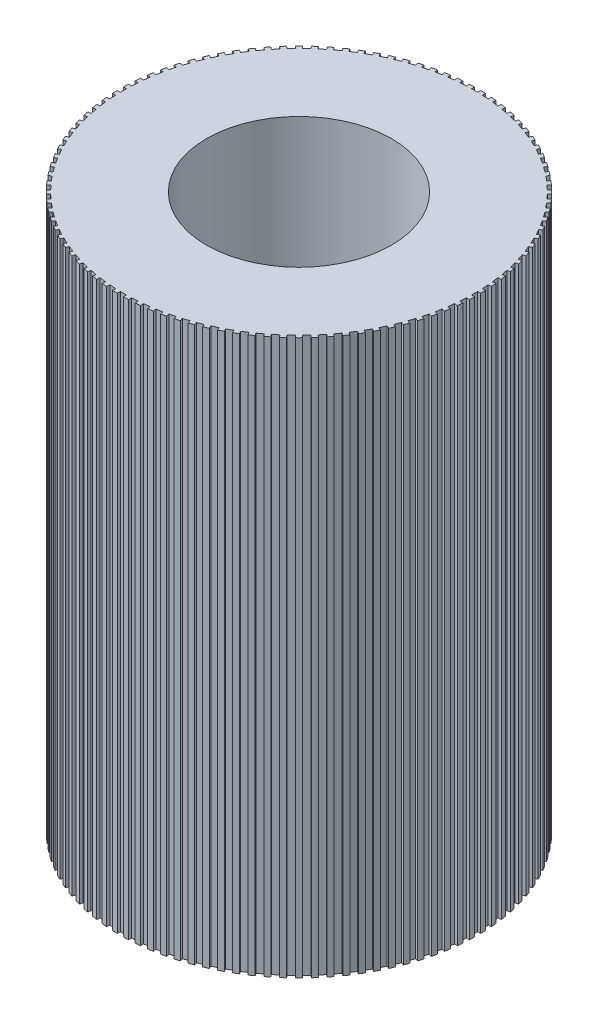
SolidWorks part; units mm, degrees
material "易切削黄铜, UNS C36000"
ref_plane "前视基准面" through (0, 0, 0) normal (0, 0, 1) x (1, 0, 0)
ref_plane "上视基准面" through (0, 0, 0) normal (0, 1, 0) x (1, 0, 0)
ref_plane "右视基准面" through (0, 0, 0) normal (1, 0, 0) x (0, 0, -1)
sketch "草图1" plane through (0, 0, 0) normal (0, 1, 0) x (1, 0, 0)
  circle A0 centre (0, 0) radius 2.9
  circle A1 centre (0, 0) radius 1.5
  dimension "D1" = 5.8
  dimension "D2" = 3
extrude "凸台-拉伸1" add sketch "草图1" along normal blind 9
sketch "草图2" plane through (0, 9, 0) normal (0, 1, 0) x (1, 0, 0)
  line L0 (0.1353, 2.9473) -> (0.2351, 2.941)
  line L1 (-0.05, 2.95) -> (0.05, 2.95)
  line L2 (-0.05, 2.95) -> (-0.05, 2.85)
  line L3 (-0.05, 2.85) -> (0.05, 2.85)
  line L4 (0.05, 2.95) -> (0.05, 2.85)
  line L5 (-0.05, 2.95) -> (0.05, 2.85) construction
  line L6 (-0.05, 2.85) -> (0.05, 2.95) construction
  line L7 (0.1353, 2.9473) -> (0.1291, 2.8475)
  line L8 (0.2351, 2.941) -> (0.2289, 2.8412)
  line L9 (0.1291, 2.8475) -> (0.2289, 2.8412)
  line L10 (0.3201, 2.933) -> (0.4193, 2.9205)
  line L11 (0.3201, 2.933) -> (0.3076, 2.8338)
  line L12 (0.4193, 2.9205) -> (0.4068, 2.8213)
  line L13 (0.3076, 2.8338) -> (0.4068, 2.8213)
  line L14 (0.5037, 2.9071) -> (0.6019, 2.8884)
  line L15 (0.5037, 2.9071) -> (0.4849, 2.8089)
  line L16 (0.6019, 2.8884) -> (0.5832, 2.7901)
  line L17 (0.4849, 2.8089) -> (0.5832, 2.7901)
  line L18 (0.6852, 2.8698) -> (0.7821, 2.8449)
  line L19 (0.6852, 2.8698) -> (0.6603, 2.7729)
  line L20 (0.7821, 2.8449) -> (0.7572, 2.748)
  line L21 (0.6603, 2.7729) -> (0.7572, 2.748)
  line L22 (0.864, 2.8211) -> (0.9592, 2.7902)
  line L23 (0.864, 2.8211) -> (0.8331, 2.726)
  line L24 (0.9592, 2.7902) -> (0.9283, 2.6951)
  line L25 (0.8331, 2.726) -> (0.9283, 2.6951)
  line L26 (1.0395, 2.7612) -> (1.1325, 2.7244)
  line L27 (1.0395, 2.7612) -> (1.0027, 2.6683)
  line L28 (1.1325, 2.7244) -> (1.0956, 2.6315)
  line L29 (1.0027, 2.6683) -> (1.0956, 2.6315)
  line L30 (1.2108, 2.6905) -> (1.3013, 2.648)
  line L31 (1.2108, 2.6905) -> (1.1682, 2.6)
  line L32 (1.3013, 2.648) -> (1.2587, 2.5575)
  line L33 (1.1682, 2.6) -> (1.2587, 2.5575)
  line L34 (1.3774, 2.6092) -> (1.465, 2.561)
  line L35 (1.3774, 2.6092) -> (1.3292, 2.5216)
  line L36 (1.465, 2.561) -> (1.4168, 2.4734)
  line L37 (1.3292, 2.5216) -> (1.4168, 2.4734)
  line L38 (1.5385, 2.5176) -> (1.6229, 2.464)
  line L39 (1.5385, 2.5176) -> (1.4849, 2.4331)
  line L40 (1.6229, 2.464) -> (1.5693, 2.3795)
  line L41 (1.4849, 2.4331) -> (1.5693, 2.3795)
  line L42 (1.6935, 2.416) -> (1.7744, 2.3572)
  line L43 (1.6935, 2.416) -> (1.6347, 2.3351)
  line L44 (1.7744, 2.3572) -> (1.7156, 2.2763)
  line L45 (1.6347, 2.3351) -> (1.7156, 2.2763)
  line L46 (1.8419, 2.3049) -> (1.9189, 2.2411)
  line L47 (1.8419, 2.3049) -> (1.7781, 2.2278)
  line L48 (1.9189, 2.2411) -> (1.8552, 2.1641)
  line L49 (1.7781, 2.2278) -> (1.8552, 2.1641)
  line L50 (1.983, 2.1847) -> (2.0559, 2.1162)
  line L51 (1.983, 2.1847) -> (1.9145, 2.1118)
  line L52 (2.0559, 2.1162) -> (1.9874, 2.0433)
  line L53 (1.9145, 2.1118) -> (1.9874, 2.0433)
  line L54 (2.1162, 2.0559) -> (2.1847, 1.983)
  line L55 (2.1162, 2.0559) -> (2.0433, 1.9874)
  line L56 (2.1847, 1.983) -> (2.1118, 1.9145)
  line L57 (2.0433, 1.9874) -> (2.1118, 1.9145)
  line L58 (2.2411, 1.9189) -> (2.3049, 1.8419)
  line L59 (2.2411, 1.9189) -> (2.1641, 1.8552)
  line L60 (2.3049, 1.8419) -> (2.2278, 1.7781)
  line L61 (2.1641, 1.8552) -> (2.2278, 1.7781)
  line L62 (2.3572, 1.7744) -> (2.416, 1.6935)
  line L63 (2.3572, 1.7744) -> (2.2763, 1.7156)
  line L64 (2.416, 1.6935) -> (2.3351, 1.6347)
  line L65 (2.2763, 1.7156) -> (2.3351, 1.6347)
  line L66 (2.464, 1.6229) -> (2.5176, 1.5385)
  line L67 (2.464, 1.6229) -> (2.3795, 1.5693)
  line L68 (2.5176, 1.5385) -> (2.4331, 1.4849)
  line L69 (2.3795, 1.5693) -> (2.4331, 1.4849)
  line L70 (2.561, 1.465) -> (2.6092, 1.3774)
  line L71 (2.561, 1.465) -> (2.4734, 1.4168)
  line L72 (2.6092, 1.3774) -> (2.5216, 1.3292)
  line L73 (2.4734, 1.4168) -> (2.5216, 1.3292)
  line L74 (2.648, 1.3013) -> (2.6905, 1.2108)
  line L75 (2.648, 1.3013) -> (2.5575, 1.2587)
  line L76 (2.6905, 1.2108) -> (2.6, 1.1682)
  line L77 (2.5575, 1.2587) -> (2.6, 1.1682)
  line L78 (2.7244, 1.1325) -> (2.7612, 1.0395)
  line L79 (2.7244, 1.1325) -> (2.6315, 1.0956)
  line L80 (2.7612, 1.0395) -> (2.6683, 1.0027)
  line L81 (2.6315, 1.0956) -> (2.6683, 1.0027)
  line L82 (2.7902, 0.9592) -> (2.8211, 0.864)
  line L83 (2.7902, 0.9592) -> (2.6951, 0.9283)
  line L84 (2.8211, 0.864) -> (2.726, 0.8331)
  line L85 (2.6951, 0.9283) -> (2.726, 0.8331)
  line L86 (2.8449, 0.7821) -> (2.8698, 0.6852)
  line L87 (2.8449, 0.7821) -> (2.748, 0.7572)
  line L88 (2.8698, 0.6852) -> (2.7729, 0.6603)
  line L89 (2.748, 0.7572) -> (2.7729, 0.6603)
  line L90 (2.8884, 0.6019) -> (2.9071, 0.5037)
  line L91 (2.8884, 0.6019) -> (2.7901, 0.5832)
  line L92 (2.9071, 0.5037) -> (2.8089, 0.4849)
  line L93 (2.7901, 0.5832) -> (2.8089, 0.4849)
  line L94 (2.9205, 0.4193) -> (2.933, 0.3201)
  line L95 (2.9205, 0.4193) -> (2.8213, 0.4068)
  line L96 (2.933, 0.3201) -> (2.8338, 0.3076)
  line L97 (2.8213, 0.4068) -> (2.8338, 0.3076)
  line L98 (2.941, 0.2351) -> (2.9473, 0.1353)
  line L99 (2.941, 0.2351) -> (2.8412, 0.2289)
  line L100 (2.9473, 0.1353) -> (2.8475, 0.1291)
  line L101 (2.8412, 0.2289) -> (2.8475, 0.1291)
  line L102 (2.95, 0.05) -> (2.95, -0.05)
  line L103 (2.95, 0.05) -> (2.85, 0.05)
  line L104 (2.95, -0.05) -> (2.85, -0.05)
  line L105 (2.85, 0.05) -> (2.85, -0.05)
  line L106 (2.9473, -0.1353) -> (2.941, -0.2351)
  line L107 (2.9473, -0.1353) -> (2.8475, -0.1291)
  line L108 (2.941, -0.2351) -> (2.8412, -0.2289)
  line L109 (2.8475, -0.1291) -> (2.8412, -0.2289)
  line L110 (2.933, -0.3201) -> (2.9205, -0.4193)
  line L111 (2.933, -0.3201) -> (2.8338, -0.3076)
  line L112 (2.9205, -0.4193) -> (2.8213, -0.4068)
  line L113 (2.8338, -0.3076) -> (2.8213, -0.4068)
  line L114 (2.9071, -0.5037) -> (2.8884, -0.6019)
  line L115 (2.9071, -0.5037) -> (2.8089, -0.4849)
  line L116 (2.8884, -0.6019) -> (2.7901, -0.5832)
  line L117 (2.8089, -0.4849) -> (2.7901, -0.5832)
  line L118 (2.8698, -0.6852) -> (2.8449, -0.7821)
  line L119 (2.8698, -0.6852) -> (2.7729, -0.6603)
  line L120 (2.8449, -0.7821) -> (2.748, -0.7572)
  line L121 (2.7729, -0.6603) -> (2.748, -0.7572)
  line L122 (2.8211, -0.864) -> (2.7902, -0.9592)
  line L123 (2.8211, -0.864) -> (2.726, -0.8331)
  line L124 (2.7902, -0.9592) -> (2.6951, -0.9283)
  line L125 (2.726, -0.8331) -> (2.6951, -0.9283)
  line L126 (2.7612, -1.0395) -> (2.7244, -1.1325)
  line L127 (2.7612, -1.0395) -> (2.6683, -1.0027)
  line L128 (2.7244, -1.1325) -> (2.6315, -1.0956)
  line L129 (2.6683, -1.0027) -> (2.6315, -1.0956)
  line L130 (2.6905, -1.2108) -> (2.648, -1.3013)
  line L131 (2.6905, -1.2108) -> (2.6, -1.1682)
  line L132 (2.648, -1.3013) -> (2.5575, -1.2587)
  line L133 (2.6, -1.1682) -> (2.5575, -1.2587)
  line L134 (2.6092, -1.3774) -> (2.561, -1.465)
  line L135 (2.6092, -1.3774) -> (2.5216, -1.3292)
  line L136 (2.561, -1.465) -> (2.4734, -1.4168)
  line L137 (2.5216, -1.3292) -> (2.4734, -1.4168)
  line L138 (2.5176, -1.5385) -> (2.464, -1.6229)
  line L139 (2.5176, -1.5385) -> (2.4331, -1.4849)
  line L140 (2.464, -1.6229) -> (2.3795, -1.5693)
  line L141 (2.4331, -1.4849) -> (2.3795, -1.5693)
  line L142 (2.416, -1.6935) -> (2.3572, -1.7744)
  line L143 (2.416, -1.6935) -> (2.3351, -1.6347)
  line L144 (2.3572, -1.7744) -> (2.2763, -1.7156)
  line L145 (2.3351, -1.6347) -> (2.2763, -1.7156)
  line L146 (2.3049, -1.8419) -> (2.2411, -1.9189)
  line L147 (2.3049, -1.8419) -> (2.2278, -1.7781)
  line L148 (2.2411, -1.9189) -> (2.1641, -1.8552)
  line L149 (2.2278, -1.7781) -> (2.1641, -1.8552)
  line L150 (2.1847, -1.983) -> (2.1162, -2.0559)
  line L151 (2.1847, -1.983) -> (2.1118, -1.9145)
  line L152 (2.1162, -2.0559) -> (2.0433, -1.9874)
  line L153 (2.1118, -1.9145) -> (2.0433, -1.9874)
  line L154 (2.0559, -2.1162) -> (1.983, -2.1847)
  line L155 (2.0559, -2.1162) -> (1.9874, -2.0433)
  line L156 (1.983, -2.1847) -> (1.9145, -2.1118)
  line L157 (1.9874, -2.0433) -> (1.9145, -2.1118)
  line L158 (1.9189, -2.2411) -> (1.8419, -2.3049)
  line L159 (1.9189, -2.2411) -> (1.8552, -2.1641)
  line L160 (1.8419, -2.3049) -> (1.7781, -2.2278)
  line L161 (1.8552, -2.1641) -> (1.7781, -2.2278)
  line L162 (1.7744, -2.3572) -> (1.6935, -2.416)
  line L163 (1.7744, -2.3572) -> (1.7156, -2.2763)
  line L164 (1.6935, -2.416) -> (1.6347, -2.3351)
  line L165 (1.7156, -2.2763) -> (1.6347, -2.3351)
  line L166 (1.6229, -2.464) -> (1.5385, -2.5176)
  line L167 (1.6229, -2.464) -> (1.5693, -2.3795)
  line L168 (1.5385, -2.5176) -> (1.4849, -2.4331)
  line L169 (1.5693, -2.3795) -> (1.4849, -2.4331)
  line L170 (1.465, -2.561) -> (1.3774, -2.6092)
  line L171 (1.465, -2.561) -> (1.4168, -2.4734)
  line L172 (1.3774, -2.6092) -> (1.3292, -2.5216)
  line L173 (1.4168, -2.4734) -> (1.3292, -2.5216)
  line L174 (1.3013, -2.648) -> (1.2108, -2.6905)
  line L175 (1.3013, -2.648) -> (1.2587, -2.5575)
  line L176 (1.2108, -2.6905) -> (1.1682, -2.6)
  line L177 (1.2587, -2.5575) -> (1.1682, -2.6)
  line L178 (1.1325, -2.7244) -> (1.0395, -2.7612)
  line L179 (1.1325, -2.7244) -> (1.0956, -2.6315)
  line L180 (1.0395, -2.7612) -> (1.0027, -2.6683)
  line L181 (1.0956, -2.6315) -> (1.0027, -2.6683)
  line L182 (0.9592, -2.7902) -> (0.864, -2.8211)
  line L183 (0.9592, -2.7902) -> (0.9283, -2.6951)
  line L184 (0.864, -2.8211) -> (0.8331, -2.726)
  line L185 (0.9283, -2.6951) -> (0.8331, -2.726)
  line L186 (0.7821, -2.8449) -> (0.6852, -2.8698)
  line L187 (0.7821, -2.8449) -> (0.7572, -2.748)
  line L188 (0.6852, -2.8698) -> (0.6603, -2.7729)
  line L189 (0.7572, -2.748) -> (0.6603, -2.7729)
  line L190 (0.6019, -2.8884) -> (0.5037, -2.9071)
  line L191 (0.6019, -2.8884) -> (0.5832, -2.7901)
  line L192 (0.5037, -2.9071) -> (0.4849, -2.8089)
  line L193 (0.5832, -2.7901) -> (0.4849, -2.8089)
  line L194 (0.4193, -2.9205) -> (0.3201, -2.933)
  line L195 (0.4193, -2.9205) -> (0.4068, -2.8213)
  line L196 (0.3201, -2.933) -> (0.3076, -2.8338)
  line L197 (0.4068, -2.8213) -> (0.3076, -2.8338)
  line L198 (0.2351, -2.941) -> (0.1353, -2.9473)
  line L199 (0.2351, -2.941) -> (0.2289, -2.8412)
  line L200 (0.1353, -2.9473) -> (0.1291, -2.8475)
  line L201 (0.2289, -2.8412) -> (0.1291, -2.8475)
  line L202 (0.05, -2.95) -> (-0.05, -2.95)
  line L203 (0.05, -2.95) -> (0.05, -2.85)
  line L204 (-0.05, -2.95) -> (-0.05, -2.85)
  line L205 (0.05, -2.85) -> (-0.05, -2.85)
  line L206 (-0.1353, -2.9473) -> (-0.2351, -2.941)
  line L207 (-0.1353, -2.9473) -> (-0.1291, -2.8475)
  line L208 (-0.2351, -2.941) -> (-0.2289, -2.8412)
  line L209 (-0.1291, -2.8475) -> (-0.2289, -2.8412)
  line L210 (-0.3201, -2.933) -> (-0.4193, -2.9205)
  line L211 (-0.3201, -2.933) -> (-0.3076, -2.8338)
  line L212 (-0.4193, -2.9205) -> (-0.4068, -2.8213)
  line L213 (-0.3076, -2.8338) -> (-0.4068, -2.8213)
  line L214 (-0.5037, -2.9071) -> (-0.6019, -2.8884)
  line L215 (-0.5037, -2.9071) -> (-0.4849, -2.8089)
  line L216 (-0.6019, -2.8884) -> (-0.5832, -2.7901)
  line L217 (-0.4849, -2.8089) -> (-0.5832, -2.7901)
  line L218 (-0.6852, -2.8698) -> (-0.7821, -2.8449)
  line L219 (-0.6852, -2.8698) -> (-0.6603, -2.7729)
  line L220 (-0.7821, -2.8449) -> (-0.7572, -2.748)
  line L221 (-0.6603, -2.7729) -> (-0.7572, -2.748)
  line L222 (-0.864, -2.8211) -> (-0.9592, -2.7902)
  line L223 (-0.864, -2.8211) -> (-0.8331, -2.726)
  line L224 (-0.9592, -2.7902) -> (-0.9283, -2.6951)
  line L225 (-0.8331, -2.726) -> (-0.9283, -2.6951)
  line L226 (-1.0395, -2.7612) -> (-1.1325, -2.7244)
  line L227 (-1.0395, -2.7612) -> (-1.0027, -2.6683)
  line L228 (-1.1325, -2.7244) -> (-1.0956, -2.6315)
  line L229 (-1.0027, -2.6683) -> (-1.0956, -2.6315)
  line L230 (-1.2108, -2.6905) -> (-1.3013, -2.648)
  line L231 (-1.2108, -2.6905) -> (-1.1682, -2.6)
  line L232 (-1.3013, -2.648) -> (-1.2587, -2.5575)
  line L233 (-1.1682, -2.6) -> (-1.2587, -2.5575)
  line L234 (-1.3774, -2.6092) -> (-1.465, -2.561)
  line L235 (-1.3774, -2.6092) -> (-1.3292, -2.5216)
  line L236 (-1.465, -2.561) -> (-1.4168, -2.4734)
  line L237 (-1.3292, -2.5216) -> (-1.4168, -2.4734)
  line L238 (-1.5385, -2.5176) -> (-1.6229, -2.464)
  line L239 (-1.5385, -2.5176) -> (-1.4849, -2.4331)
  line L240 (-1.6229, -2.464) -> (-1.5693, -2.3795)
  line L241 (-1.4849, -2.4331) -> (-1.5693, -2.3795)
  line L242 (-1.6935, -2.416) -> (-1.7744, -2.3572)
  line L243 (-1.6935, -2.416) -> (-1.6347, -2.3351)
  line L244 (-1.7744, -2.3572) -> (-1.7156, -2.2763)
  line L245 (-1.6347, -2.3351) -> (-1.7156, -2.2763)
  line L246 (-1.8419, -2.3049) -> (-1.9189, -2.2411)
  line L247 (-1.8419, -2.3049) -> (-1.7781, -2.2278)
  line L248 (-1.9189, -2.2411) -> (-1.8552, -2.1641)
  line L249 (-1.7781, -2.2278) -> (-1.8552, -2.1641)
  line L250 (-1.983, -2.1847) -> (-2.0559, -2.1162)
  line L251 (-1.983, -2.1847) -> (-1.9145, -2.1118)
  line L252 (-2.0559, -2.1162) -> (-1.9874, -2.0433)
  line L253 (-1.9145, -2.1118) -> (-1.9874, -2.0433)
  line L254 (-2.1162, -2.0559) -> (-2.1847, -1.983)
  line L255 (-2.1162, -2.0559) -> (-2.0433, -1.9874)
  line L256 (-2.1847, -1.983) -> (-2.1118, -1.9145)
  line L257 (-2.0433, -1.9874) -> (-2.1118, -1.9145)
  line L258 (-2.2411, -1.9189) -> (-2.3049, -1.8419)
  line L259 (-2.2411, -1.9189) -> (-2.1641, -1.8552)
  line L260 (-2.3049, -1.8419) -> (-2.2278, -1.7781)
  line L261 (-2.1641, -1.8552) -> (-2.2278, -1.7781)
  line L262 (-2.3572, -1.7744) -> (-2.416, -1.6935)
  line L263 (-2.3572, -1.7744) -> (-2.2763, -1.7156)
  line L264 (-2.416, -1.6935) -> (-2.3351, -1.6347)
  line L265 (-2.2763, -1.7156) -> (-2.3351, -1.6347)
  line L266 (-2.464, -1.6229) -> (-2.5176, -1.5385)
  line L267 (-2.464, -1.6229) -> (-2.3795, -1.5693)
  line L268 (-2.5176, -1.5385) -> (-2.4331, -1.4849)
  line L269 (-2.3795, -1.5693) -> (-2.4331, -1.4849)
  line L270 (-2.561, -1.465) -> (-2.6092, -1.3774)
  line L271 (-2.561, -1.465) -> (-2.4734, -1.4168)
  line L272 (-2.6092, -1.3774) -> (-2.5216, -1.3292)
  line L273 (-2.4734, -1.4168) -> (-2.5216, -1.3292)
  line L274 (-2.648, -1.3013) -> (-2.6905, -1.2108)
  line L275 (-2.648, -1.3013) -> (-2.5575, -1.2587)
  line L276 (-2.6905, -1.2108) -> (-2.6, -1.1682)
  line L277 (-2.5575, -1.2587) -> (-2.6, -1.1682)
  line L278 (-2.7244, -1.1325) -> (-2.7612, -1.0395)
  line L279 (-2.7244, -1.1325) -> (-2.6315, -1.0956)
  line L280 (-2.7612, -1.0395) -> (-2.6683, -1.0027)
  line L281 (-2.6315, -1.0956) -> (-2.6683, -1.0027)
  line L282 (-2.7902, -0.9592) -> (-2.8211, -0.864)
  line L283 (-2.7902, -0.9592) -> (-2.6951, -0.9283)
  line L284 (-2.8211, -0.864) -> (-2.726, -0.8331)
  line L285 (-2.6951, -0.9283) -> (-2.726, -0.8331)
  line L286 (-2.8449, -0.7821) -> (-2.8698, -0.6852)
  line L287 (-2.8449, -0.7821) -> (-2.748, -0.7572)
  line L288 (-2.8698, -0.6852) -> (-2.7729, -0.6603)
  line L289 (-2.748, -0.7572) -> (-2.7729, -0.6603)
  line L290 (-2.8884, -0.6019) -> (-2.9071, -0.5037)
  line L291 (-2.8884, -0.6019) -> (-2.7901, -0.5832)
  line L292 (-2.9071, -0.5037) -> (-2.8089, -0.4849)
  line L293 (-2.7901, -0.5832) -> (-2.8089, -0.4849)
  line L294 (-2.9205, -0.4193) -> (-2.933, -0.3201)
  line L295 (-2.9205, -0.4193) -> (-2.8213, -0.4068)
  line L296 (-2.933, -0.3201) -> (-2.8338, -0.3076)
  line L297 (-2.8213, -0.4068) -> (-2.8338, -0.3076)
  line L298 (-2.941, -0.2351) -> (-2.9473, -0.1353)
  line L299 (-2.941, -0.2351) -> (-2.8412, -0.2289)
  line L300 (-2.9473, -0.1353) -> (-2.8475, -0.1291)
  line L301 (-2.8412, -0.2289) -> (-2.8475, -0.1291)
  line L302 (-2.95, -0.05) -> (-2.95, 0.05)
  line L303 (-2.95, -0.05) -> (-2.85, -0.05)
  line L304 (-2.95, 0.05) -> (-2.85, 0.05)
  line L305 (-2.85, -0.05) -> (-2.85, 0.05)
  line L306 (-2.9473, 0.1353) -> (-2.941, 0.2351)
  line L307 (-2.9473, 0.1353) -> (-2.8475, 0.1291)
  line L308 (-2.941, 0.2351) -> (-2.8412, 0.2289)
  line L309 (-2.8475, 0.1291) -> (-2.8412, 0.2289)
  line L310 (-2.933, 0.3201) -> (-2.9205, 0.4193)
  line L311 (-2.933, 0.3201) -> (-2.8338, 0.3076)
  line L312 (-2.9205, 0.4193) -> (-2.8213, 0.4068)
  line L313 (-2.8338, 0.3076) -> (-2.8213, 0.4068)
  line L314 (-2.9071, 0.5037) -> (-2.8884, 0.6019)
  line L315 (-2.9071, 0.5037) -> (-2.8089, 0.4849)
  line L316 (-2.8884, 0.6019) -> (-2.7901, 0.5832)
  line L317 (-2.8089, 0.4849) -> (-2.7901, 0.5832)
  line L318 (-2.8698, 0.6852) -> (-2.8449, 0.7821)
  line L319 (-2.8698, 0.6852) -> (-2.7729, 0.6603)
  line L320 (-2.8449, 0.7821) -> (-2.748, 0.7572)
  line L321 (-2.7729, 0.6603) -> (-2.748, 0.7572)
  line L322 (-2.8211, 0.864) -> (-2.7902, 0.9592)
  line L323 (-2.8211, 0.864) -> (-2.726, 0.8331)
  line L324 (-2.7902, 0.9592) -> (-2.6951, 0.9283)
  line L325 (-2.726, 0.8331) -> (-2.6951, 0.9283)
  line L326 (-2.7612, 1.0395) -> (-2.7244, 1.1325)
  line L327 (-2.7612, 1.0395) -> (-2.6683, 1.0027)
  line L328 (-2.7244, 1.1325) -> (-2.6315, 1.0956)
  line L329 (-2.6683, 1.0027) -> (-2.6315, 1.0956)
  line L330 (-2.6905, 1.2108) -> (-2.648, 1.3013)
  line L331 (-2.6905, 1.2108) -> (-2.6, 1.1682)
  line L332 (-2.648, 1.3013) -> (-2.5575, 1.2587)
  line L333 (-2.6, 1.1682) -> (-2.5575, 1.2587)
  line L334 (-2.6092, 1.3774) -> (-2.561, 1.465)
  line L335 (-2.6092, 1.3774) -> (-2.5216, 1.3292)
  line L336 (-2.561, 1.465) -> (-2.4734, 1.4168)
  line L337 (-2.5216, 1.3292) -> (-2.4734, 1.4168)
  line L338 (-2.5176, 1.5385) -> (-2.464, 1.6229)
  line L339 (-2.5176, 1.5385) -> (-2.4331, 1.4849)
  line L340 (-2.464, 1.6229) -> (-2.3795, 1.5693)
  line L341 (-2.4331, 1.4849) -> (-2.3795, 1.5693)
  line L342 (-2.416, 1.6935) -> (-2.3572, 1.7744)
  line L343 (-2.416, 1.6935) -> (-2.3351, 1.6347)
  line L344 (-2.3572, 1.7744) -> (-2.2763, 1.7156)
  line L345 (-2.3351, 1.6347) -> (-2.2763, 1.7156)
  line L346 (-2.3049, 1.8419) -> (-2.2411, 1.9189)
  line L347 (-2.3049, 1.8419) -> (-2.2278, 1.7781)
  line L348 (-2.2411, 1.9189) -> (-2.1641, 1.8552)
  line L349 (-2.2278, 1.7781) -> (-2.1641, 1.8552)
  line L350 (-2.1847, 1.983) -> (-2.1162, 2.0559)
  line L351 (-2.1847, 1.983) -> (-2.1118, 1.9145)
  line L352 (-2.1162, 2.0559) -> (-2.0433, 1.9874)
  line L353 (-2.1118, 1.9145) -> (-2.0433, 1.9874)
  line L354 (-2.0559, 2.1162) -> (-1.983, 2.1847)
  line L355 (-2.0559, 2.1162) -> (-1.9874, 2.0433)
  line L356 (-1.983, 2.1847) -> (-1.9145, 2.1118)
  line L357 (-1.9874, 2.0433) -> (-1.9145, 2.1118)
  line L358 (-1.9189, 2.2411) -> (-1.8419, 2.3049)
  line L359 (-1.9189, 2.2411) -> (-1.8552, 2.1641)
  line L360 (-1.8419, 2.3049) -> (-1.7781, 2.2278)
  line L361 (-1.8552, 2.1641) -> (-1.7781, 2.2278)
  line L362 (-1.7744, 2.3572) -> (-1.6935, 2.416)
  line L363 (-1.7744, 2.3572) -> (-1.7156, 2.2763)
  line L364 (-1.6935, 2.416) -> (-1.6347, 2.3351)
  line L365 (-1.7156, 2.2763) -> (-1.6347, 2.3351)
  line L366 (-1.6229, 2.464) -> (-1.5385, 2.5176)
  line L367 (-1.6229, 2.464) -> (-1.5693, 2.3795)
  line L368 (-1.5385, 2.5176) -> (-1.4849, 2.4331)
  line L369 (-1.5693, 2.3795) -> (-1.4849, 2.4331)
  line L370 (-1.465, 2.561) -> (-1.3774, 2.6092)
  line L371 (-1.465, 2.561) -> (-1.4168, 2.4734)
  line L372 (-1.3774, 2.6092) -> (-1.3292, 2.5216)
  line L373 (-1.4168, 2.4734) -> (-1.3292, 2.5216)
  line L374 (-1.3013, 2.648) -> (-1.2108, 2.6905)
  line L375 (-1.3013, 2.648) -> (-1.2587, 2.5575)
  line L376 (-1.2108, 2.6905) -> (-1.1682, 2.6)
  line L377 (-1.2587, 2.5575) -> (-1.1682, 2.6)
  line L378 (-1.1325, 2.7244) -> (-1.0395, 2.7612)
  line L379 (-1.1325, 2.7244) -> (-1.0956, 2.6315)
  line L380 (-1.0395, 2.7612) -> (-1.0027, 2.6683)
  line L381 (-1.0956, 2.6315) -> (-1.0027, 2.6683)
  line L382 (-0.9592, 2.7902) -> (-0.864, 2.8211)
  line L383 (-0.9592, 2.7902) -> (-0.9283, 2.6951)
  line L384 (-0.864, 2.8211) -> (-0.8331, 2.726)
  line L385 (-0.9283, 2.6951) -> (-0.8331, 2.726)
  line L386 (-0.7821, 2.8449) -> (-0.6852, 2.8698)
  line L387 (-0.7821, 2.8449) -> (-0.7572, 2.748)
  line L388 (-0.6852, 2.8698) -> (-0.6603, 2.7729)
  line L389 (-0.7572, 2.748) -> (-0.6603, 2.7729)
  line L390 (-0.6019, 2.8884) -> (-0.5037, 2.9071)
  line L391 (-0.6019, 2.8884) -> (-0.5832, 2.7901)
  line L392 (-0.5037, 2.9071) -> (-0.4849, 2.8089)
  line L393 (-0.5832, 2.7901) -> (-0.4849, 2.8089)
  line L394 (-0.4193, 2.9205) -> (-0.3201, 2.933)
  line L395 (-0.4193, 2.9205) -> (-0.4068, 2.8213)
  line L396 (-0.3201, 2.933) -> (-0.3076, 2.8338)
  line L397 (-0.4068, 2.8213) -> (-0.3076, 2.8338)
  line L398 (-0.2351, 2.941) -> (-0.1353, 2.9473)
  line L399 (-0.2351, 2.941) -> (-0.2289, 2.8412)
  line L400 (-0.1353, 2.9473) -> (-0.1291, 2.8475)
  line L401 (-0.2289, 2.8412) -> (-0.1291, 2.8475)
  circle A0 centre (0, 0) radius 2.9 construction
  point P0 (0, 2.9)
  point P407 (0, 0)
  dimension "D1" = 0.1
  dimension "D2" = 0.1
  dimension "D3" = 100
extrude "切除-拉伸1" cut sketch "草图2" against normal blind 9
